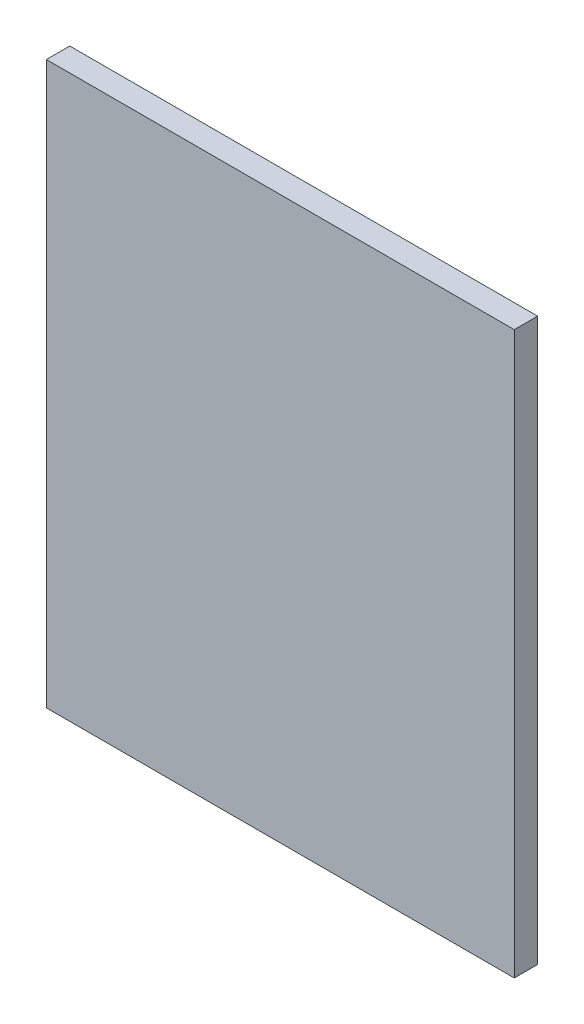
SolidWorks part; units mm, degrees
ref_plane "Front Plane" through (0, 0, 0) normal (0, 0, 1) x (1, 0, 0)
ref_plane "Top Plane" through (0, 0, 0) normal (0, 1, 0) x (1, 0, 0)
ref_plane "Right Plane" through (0, 0, 0) normal (1, 0, 0) x (0, 0, -1)
sketch "Sketch1" plane through (0, 0, 0) normal (0, 0, 1) x (1, 0, 0)
  line L0 (4.4664, -40.741) -> (4.4664, 111.659) construction
  line L1 (-59.0336, -40.741) -> (67.9664, -40.741)
  line L2 (-59.0336, -40.741) -> (-59.0336, 111.659)
  line L3 (-59.0336, 111.659) -> (67.9664, 111.659)
  line L4 (67.9664, -40.741) -> (67.9664, 111.659)
  dimension "D1" = 127
  dimension "D2" = 152.4
extrude "Boss-Extrude1" add sketch "Sketch1" along normal blind 6.35
